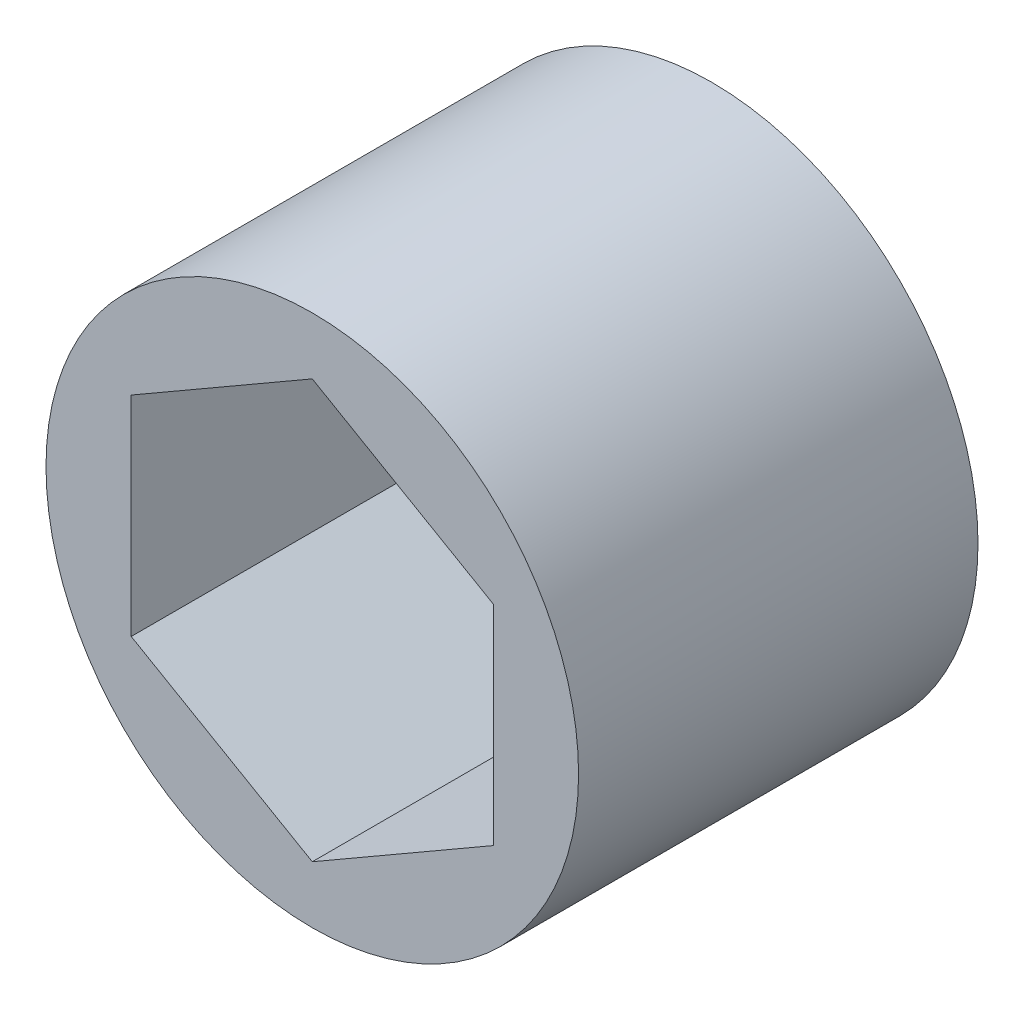
SolidWorks part; units mm, degrees
material "PET"
ref_plane "Front Plane" through (0, 0, 0) normal (0, 0, 1) x (1, 0, 0)
ref_plane "Top Plane" through (0, 0, 0) normal (0, 1, 0) x (1, 0, 0)
ref_plane "Right Plane" through (0, 0, 0) normal (1, 0, 0) x (0, 0, -1)
sketch "Sketch1" plane through (0, 0, 0) normal (0, 0, 1) x (1, 0, 0)
  line L1 (0, 7.479) -> (-6.477, 3.7395)
  line L2 (-6.477, 3.7395) -> (-6.477, -3.7395)
  line L3 (-6.477, -3.7395) -> (0, -7.479)
  line L4 (0, -7.479) -> (6.477, -3.7395)
  line L5 (6.477, -3.7395) -> (6.477, 3.7395)
  line L6 (6.477, 3.7395) -> (0, 7.479)
  circle A0 centre (0, 0) radius 9.525
  circle A1 centre (0, 0) radius 6.477 construction
  dimension "D1" = 12.954
  dimension "D2" = 19.05
extrude "Boss-Extrude1" add sketch "Sketch1" along normal mid plane 14.2875
